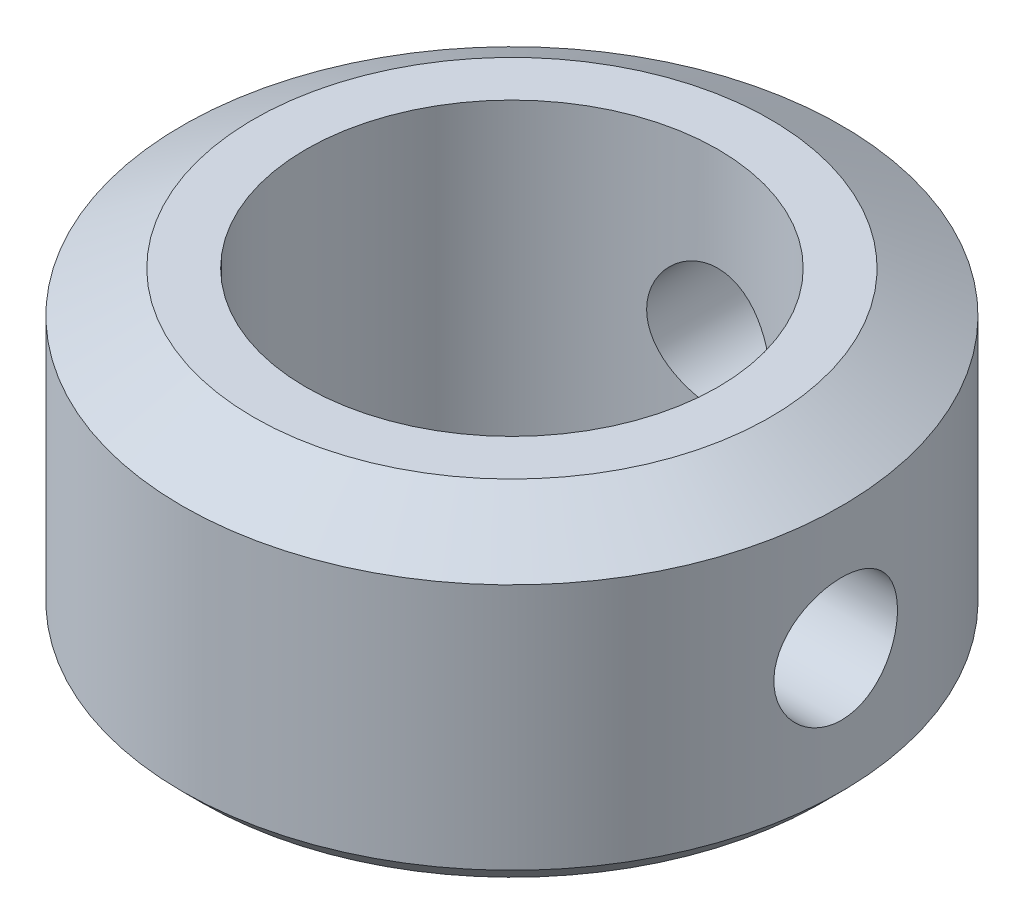
SolidWorks part; units mm, degrees
material "1060 Alloy"
ref_plane "Front Plane" through (0, 0, 0) normal (0, 0, 1) x (1, 0, 0)
ref_plane "Top Plane" through (0, 0, 0) normal (0, 1, 0) x (1, 0, 0)
ref_plane "Right Plane" through (0, 0, 0) normal (1, 0, 0) x (0, 0, -1)
sketch "Sketch1" plane through (0, 0, 0) normal (0, 1, 0) x (1, 0, 0)
  circle A0 centre (0, 0) radius 5
  circle A1 centre (0, 0) radius 8
  dimension "D1" = 10
  dimension "D2" = 16
extrude "Boss-Extrude1" add sketch "Sketch1" along normal blind 7.5
chamfer "Chamfer1" distance 1 angle 60 1 edges at (0, 7.5, 8) first distance on face at (0, 7.5, 8)
chamfer "Chamfer2" distance 0.5 angle 45 1 edges at (0, 0, 8)
chamfer "Chamfer3" distance 0.2 angle 45 1 edges at (0, 0, 5)
ref_plane "Plane1" through (8, 0, 0) normal (1, 0, 0) x (0, 0, -1)
sketch "Sketch2" plane through (8, 0, 0) normal (1, 0, 0) x (0, 0, -1)
  line L0 (-8, 0.5) -> (8, 0.5) construction
  line L3 (0, 6.5) -> (0, 0.5) construction
  line L4 (-8, 6.5) -> (8, 6.5) construction
  circle A0 centre (0, 3.5) radius 1.5
  dimension "D1" = 3
  dimension "D2" = 3.5
extrude "Cut-Extrude1" cut sketch "Sketch2" against normal up to next
ref_axis "Axis1" through (0, 7.5, 0) along (0, -1, 0)
pattern_circular "CirPattern1" count 2 every 90 about axis through (0, 7.5, 0) along (0, -1, 0) of "Cut-Extrude1" reverse direction yes
ref_plane "planmedianpouliegt2" through (0, 11, 0) normal (0, 1, 0) x (1, 0, 0)
